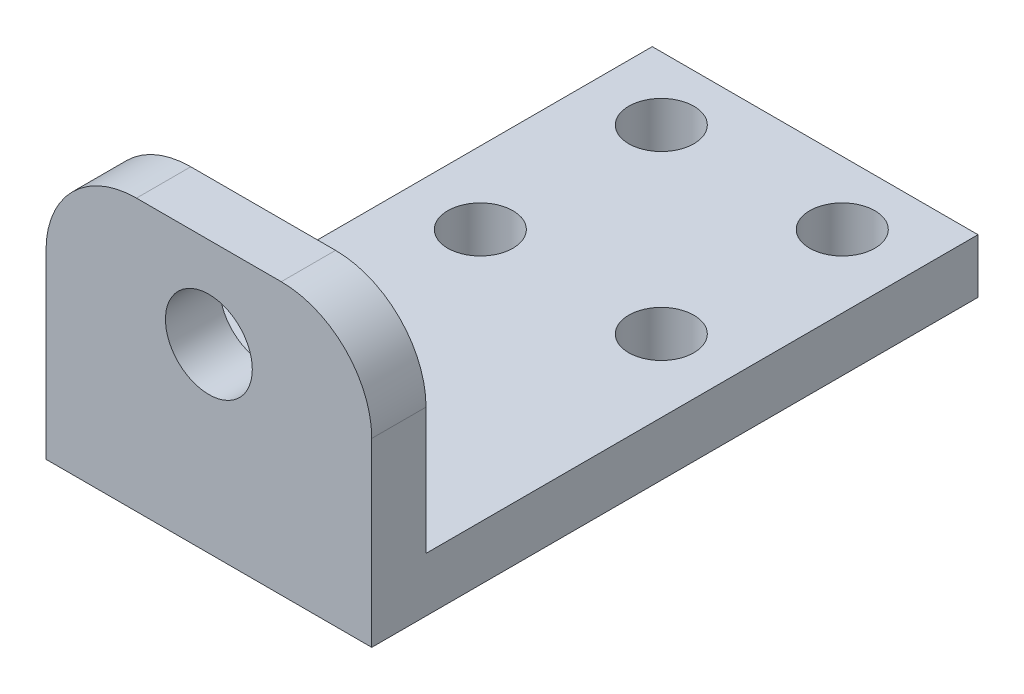
SolidWorks part; units mm, degrees
ref_plane "Front Plane" through (0, 0, 0) normal (0, 0, 1) x (1, 0, 0)
ref_plane "Top Plane" through (0, 0, 0) normal (0, 1, 0) x (1, 0, 0)
ref_plane "Right Plane" through (0, 0, 0) normal (1, 0, 0) x (0, 0, -1)
sketch "Sketch1" plane through (0, 0, 0) normal (1, 0, 0) x (0, 0, -1)
  line L0 (0, 0) -> (33.5, 0)
  line L1 (33.5, 0) -> (33.5, 3)
  line L2 (33.5, 3) -> (3, 3)
  line L3 (3, 3) -> (3, 15)
  line L4 (3, 15) -> (0, 15)
  line L5 (0, 15) -> (0, 0)
  dimension "D1" = 3
  dimension "D2" = 15
  dimension "D3" = 33.5
extrude "Boss-Extrude1" add sketch "Sketch1" along normal blind 18
sketch "Sketch2" plane through (0, 0, 0) normal (0, 0, 1) x (1, 0, 0)
  line L0 (0, 0) -> (18, 0) construction
  line L2 (9, 0) -> (9, 10) construction
  line L3 (18, 15) -> (0, 15) construction
  point P7 (9, 10)
  point P13 (9, 10)
  dimension "D1" = 5
hole_wizard "M4 Clearance Hole1" positions "Sketch2" profile "Sketch3" hole size "M4" standard "ANSI Metric"
sketch "Sketch3" plane through (9, 10, 0) normal (1, 0, 0) x (0, -1, 0)
  line L0 (0, 0) -> (0, 4.4421)
  line L1 (0, 4.4421) -> (2.4, 3)
  line L2 (2.4, 3) -> (2.4, 0)
  line L5 (2.4, 0) -> (0, 0)
  line L10 (0, 4.4421) -> (-2.4, 3) construction
  line L11 (0, -6.35) -> (0, 107.95) construction
  dimension "Hole Dia." = 4.8
  dimension "Hole Depth" = 3
  dimension "Drill Angle" = 118
fillet "Fillet1" radius 5 2 edges at (0, 15, -1.5) (18, 15, -1.5)
sketch "Sketch4" plane through (0, 3, 0) normal (0, 1, 0) x (1, 0, 0)
  line L0 (9, 33.5) -> (9, 3) construction
  line L1 (18, 33.5) -> (0, 33.5) construction
  line L2 (18, 3) -> (0, 3) construction
  line L4 (18, 25) -> (0, 25) construction
  line L7 (0, 33.5) -> (0, 3) construction
  line L8 (18, 33.5) -> (18, 3) construction
  point P42 (4, 30)
  point P45 (4, 20)
  point P46 (14, 20)
  point P47 (14, 30)
  dimension "D1" = 5
  dimension "D2" = 5
  dimension "D3" = 8.5
hole_wizard "M3 Clearance Hole1" positions "Sketch4" profile "Sketch5" hole size "M3" standard "ANSI Metric" end condition through all
sketch "Sketch5" plane through (14, 3, -30) normal (1, 0, 0) x (0, 0, 1)
  line L0 (0, 0) -> (0, 3)
  line L1 (0, 3) -> (1.8, 3)
  line L2 (1.8, 3) -> (1.8, 0)
  line L5 (1.8, 0) -> (0, 0)
  line L11 (0, -6.35) -> (0, 107.95) construction
  dimension "Thru Hole Dia." = 3.6
  dimension "Thru Hole Depth" = 3
